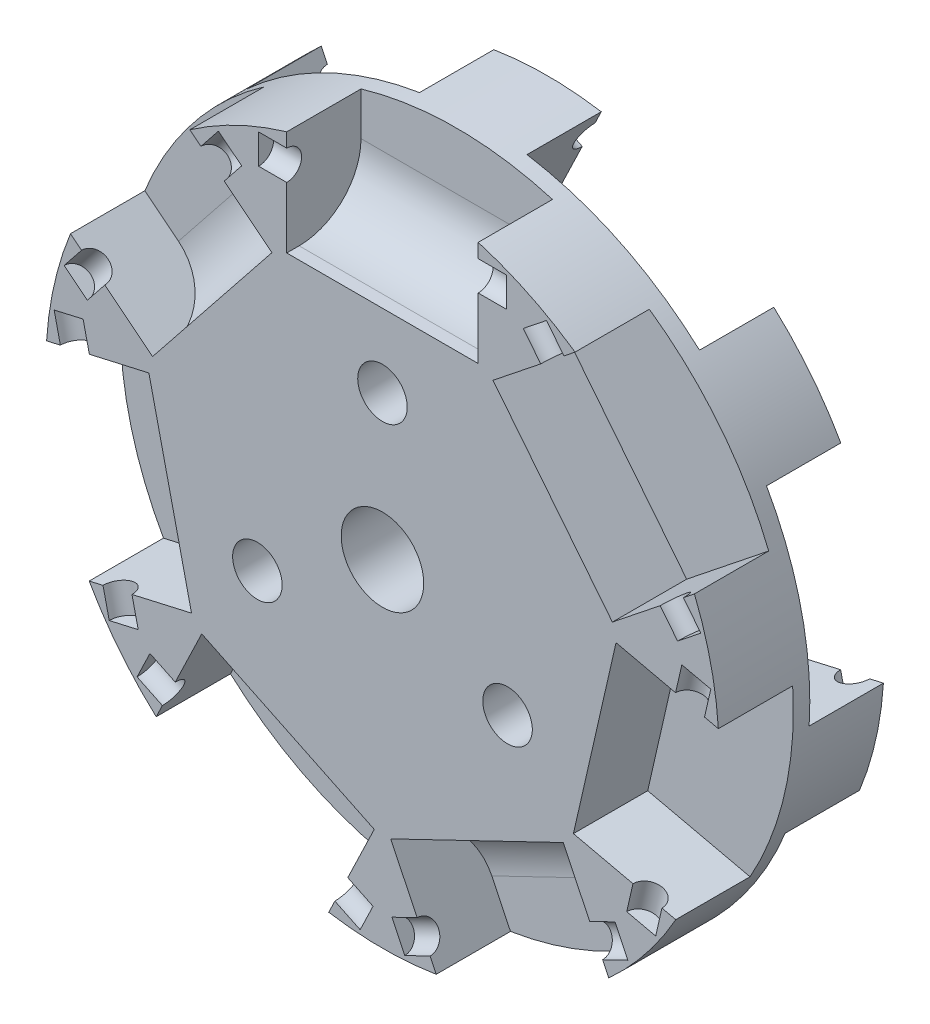
SolidWorks part; units mm, degrees
other "Markup1"
sketch "Sketch8" plane through (32.7336, 32.7336, 0) normal (0.5701, 0.1846, 0.8006) x (0.8043, 0.0736, -0.5897)
ref_plane "Front Plane" through (0, 0, 0) normal (0, 0, 1) x (1, 0, 0)
ref_plane "Top Plane" through (0, 0, 0) normal (0, 1, 0) x (1, 0, 0)
ref_plane "Right Plane" through (0, 0, 0) normal (1, 0, 0) x (0, 0, -1)
sketch "Sketch1" plane through (0, 0, 0) normal (0, 0, 1) x (1, 0, 0)
  circle A0 centre (0, 0) radius 25.8953
  dimension "D1" = 51.7906
extrude "Boss-Extrude2" add sketch "Sketch1" against normal blind 6.35
sketch "Sketch2" plane through (0, 0, 0) normal (0, 0, 1) x (1, 0, 0)
  line L1 (-12.7, 25.8953) -> (12.7, 25.8953) construction
  line L2 (-7.366, 27.1653) -> (7.366, 27.1653)
  line L3 (-7.366, 27.1653) -> (-7.366, 16.7513)
  line L4 (-7.366, 16.7513) -> (7.366, 16.7513)
  line L5 (7.366, 27.1653) -> (7.366, 16.7513)
  line L6 (-7.366, 27.1653) -> (7.366, 16.7513) construction
  line L7 (-7.366, 16.7513) -> (7.366, 27.1653) construction
  line L35 (0, 0) -> (0, 25.8953) construction
  circle A1 centre (0, 0) radius 25.8953 construction
  point P10 (0, 21.9583)
  circle M7 centre (0, 0) radius 25.8953
  dimension "D1" = 14.732
  dimension "D2" = 10.414
  dimension "D3" = 1.27
  dimension "D4" = 25.4
extrude "Cut-Extrude2" cut sketch "Sketch2" against normal blind 5.715 contours L5 L3 L4 M7 | L3 L2 L5 L4 region at (0, 21.1523, 0)
pattern_circular "CirPattern1" count 7 over 360 about axis through (0, 0, 0) along (0, 0, 1) of "Cut-Extrude2"
ref_plane "Plane1" through (0, 0, 0) normal (1, 0, 0) x (0, 0, -1)
sketch "Sketch4" plane through (0, 0, 0) normal (1, 0, 0) x (0, 0, -1)
  line L0 (5.715, 16.7513) -> (0, 16.7513) construction
  circle A0 centre (0, 22.5933) radius 1.143
  dimension "D1" = 2.286
  dimension "D2" = 5.842
extrude "Cut-Extrude4" cut sketch "Sketch4" against normal mid plane 19.05
pattern_circular "CirPattern2" count 7 over 360 about axis through (0, 0, 0) along (0, 0, 1) of "Cut-Extrude4"
sketch "Sketch5" plane through (0, 0, 0) normal (0, 0, 1) x (1, 0, 0)
  circle A0 centre (0, 0) radius 3.175
  dimension "D1" = 6.35
extrude "Cut-Extrude5" cut sketch "Sketch5" against normal through all
sketch "Sketch6" plane through (0, 0, -6.35) normal (0, 0, -1) x (-1, 0, 0)
  circle A4 centre (0, 11.1125) radius 1.905
  circle A5 centre (9.6237, -5.5562) radius 1.905
  circle A6 centre (-9.6237, -5.5562) radius 1.905
  point P3 (-13.0006, -8.1254)
  point P4 (0, 0)
  point P8 (0, 0)
  dimension "D1" = 3.81
  dimension "D2" = 11.1125
extrude "Cut-Extrude7" cut sketch "Sketch6" against normal through all
sketch "Sketch9" plane through (0, 0, -6.35) normal (0, 0, -1) x (-1, 0, 0)
  circle A0 centre (0, 0) radius 25.8953
  circle A5 centre (9.6237, -5.5562) radius 1.905 construction
  circle A6 centre (-9.6237, -5.5562) radius 1.905 construction
  circle A7 centre (0, 11.1125) radius 1.905 construction
  circle A8 centre (9.6237, -5.5562) radius 1.905
  circle A9 centre (0, 0) radius 25.8953 construction
  circle A10 centre (0, 0) radius 3.175 construction
  circle A11 centre (0, 0) radius 3.175
  circle A12 centre (-9.6237, -5.5562) radius 1.905
  circle A13 centre (0, 11.1125) radius 1.905
extrude "Boss-Extrude3" add sketch "Sketch9" along normal blind 6.35
sketch "Sketch10" plane through (0, 0, -12.7) normal (0, 0, -1) x (-1, 0, 0)
  line L0 (-23.9355, 23.3309) -> (1.4645, 23.3309) construction
  line L1 (-0.6316, 18.2884) -> (-13.9047, 11.8964)
  line L2 (-0.6316, 18.2884) -> (-5.15, 27.6711)
  line L3 (-5.15, 27.6711) -> (-18.4231, 21.2791)
  line L4 (-13.9047, 11.8964) -> (-18.4231, 21.2791)
  line L5 (-0.6316, 18.2884) -> (-18.4231, 21.2791) construction
  line L6 (-5.15, 27.6711) -> (-13.9047, 11.8964) construction
  line L7 (0, 0) -> (-11.2355, 23.3309) construction
  line L8 (0, 0) -> (0, 40.3277) construction
  circle A2 centre (0, 0) radius 25.8953 construction
  point P8 (-9.5273, 19.7837)
  dimension "D1" = 1.27
  dimension "D2" = 14.732
  dimension "D3" = 10.414
  dimension "D4" = 25.4
  dimension "D5" = 25.714
extrude "Cut-Extrude8" cut sketch "Sketch10" against normal blind 5.715
pattern_circular "CirPattern3" count 7 over 360 about axis through (0, 0, -12.7) along (0, 0, -1) of "Cut-Extrude8"
ref_plane "Plane2" through (0, 0, 0) normal (-0.901, 0.4339, 0) x (0, 0, -1)
sketch "Sketch11" plane through (0, 0, 0) normal (-0.901, 0.4339, 0) x (0, 0, -1)
  line L5 (6.985, -16.7513) -> (12.7, -16.7513) construction
  line L6 (12.7, -24.8256) -> (12.7, -21.2375) construction
  circle A0 centre (12.7, -22.5933) radius 1.143
  dimension "D1" = 2.286
  dimension "D2" = 5.842
extrude "Cut-Extrude9" cut sketch "Sketch11" against normal mid plane 19.05
pattern_circular "CirPattern4" count 7 over 360 about axis through (0, 0, -12.7) along (0, 0, -1) of "Cut-Extrude9"
fillet "Fillet1" radius 4.7625 10 edges at (16.3313, 3.7275, -6.985) (13.0967, -10.4443, -6.985) (0, -16.7513, -6.985) (7.2681, 15.0924, -6.985) (-13.0967, -10.4443, -6.985) (-16.3313, -3.7275, -5.715) (-7.2681, -15.0924, -5.715) (7.2681, -15.0924, -5.715) (0, 16.7513, -5.715) (-13.0967, 10.4443, -5.715)
